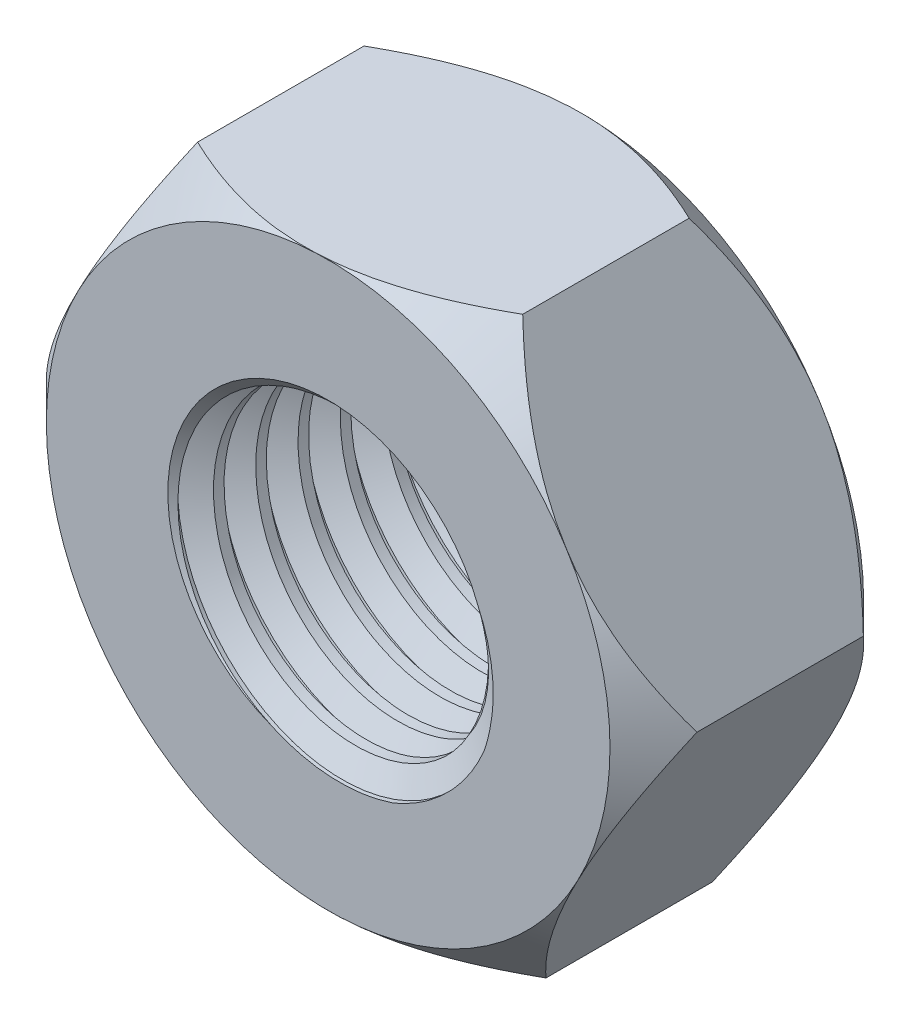
SolidWorks part; units mm, degrees
ref_plane "Front Plane" through (0, 0, 0) normal (0, 0, 1) x (1, 0, 0)
ref_plane "Top Plane" through (0, 0, 0) normal (0, 1, 0) x (1, 0, 0)
ref_plane "Right Plane" through (0, 0, 0) normal (1, 0, 0) x (0, 0, -1)
sketch "Sketch2" plane through (0, 0, 0) normal (0, 0, 1) x (1, 0, 0)
  line L1 (-11.5372, -0.4769) -> (-5.3555, -10.2299)
  line L2 (-5.3555, -10.2299) -> (6.1816, -9.753)
  line L3 (6.1816, -9.753) -> (11.5372, 0.4769)
  line L4 (11.5372, 0.4769) -> (5.3555, 10.2299)
  line L5 (5.3555, 10.2299) -> (-6.1816, 9.753)
  line L6 (-6.1816, 9.753) -> (-11.5372, -0.4769)
  circle A0 centre (0, 0) radius 10 construction
  dimension "D1" = 20
extrude "Boss-Extrude1" add sketch "Sketch2" along normal mid plane 9
sketch "Sketch3" plane through (0, 0, 4.5) normal (0, 0, 1) x (1, 0, 0)
  line L0 (-6.1816, 9.753) -> (-11.5372, -0.4769) construction
  circle A0 centre (0, 0) radius 10
extrude "Cut-Extrude1" cut sketch "Sketch3" against normal through all draft 45 flip side to cut
mirror "Mirror1" about plane through (0, 0, 0) normal (0, 0, 1) of "Cut-Extrude1"
sketch "Sketch4" plane through (0, 0, 4.5) normal (0, 0, 1) x (1, 0, 0)
  circle A0 centre (0, 0) radius 5.19
  dimension "D1" = 10.38
extrude "Cut-Extrude2" cut sketch "Sketch4" against normal through all
chamfer "Chamfer1" distance 0.5 angle 45 2 edges at (5.19, 0, -4.5) (5.19, 0, 4.5)
thread "Thread1" pitch 1.5 method cut profile "Thread Profile1" start angle 0, offset 2, length 0, pitch 1.5, diameter 10.38
ref_plane "Plane1" through (-5.19, 0, 6) normal (0, -1, 0) x (-1, 0, 0)
sketch "Thread Profile1" plane through (-5.19, 0, 6) normal (0, -1, 0) x (-1, 0, 0)
  line L0 (0, 0) -> (0, 1.5) construction
  line L1 (0, 0) -> (0.8119, 0.4687)
  line L2 (0.8119, 0.4687) -> (0.8119, 0.6562)
  line L3 (0.8119, 0.6562) -> (0, 1.125)
  line L4 (0.8119, 0.5625) -> (0, 0.5625) construction
  line L11 (0, 0) -> (0, 1.125)
  point P2 (0, 0)
  dimension "Pitch" = 1.5
  dimension "Profile_Angle" = 60
  dimension "Profile_Land" = 0.1875
  dimension "Profile_Height" = 0.8119
